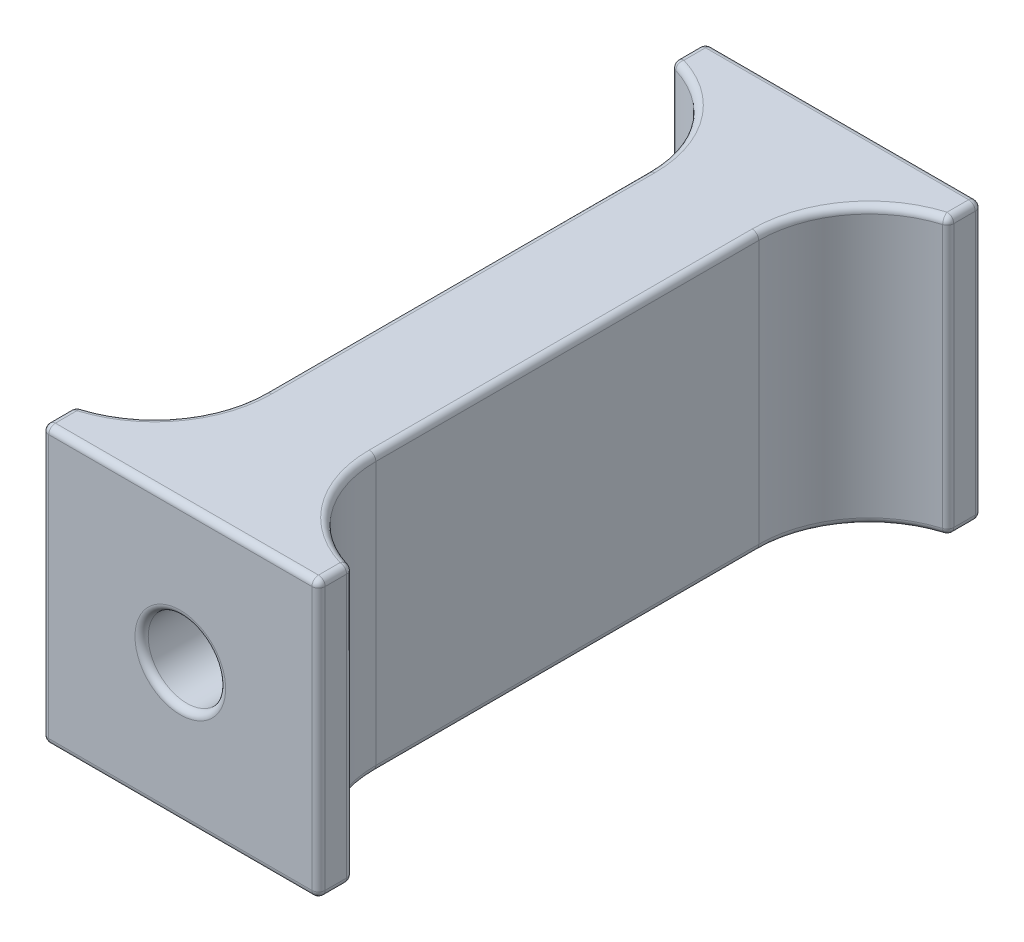
SolidWorks part; units mm, degrees
ref_plane "Alzado" through (0, 0, 0) normal (0, 0, 1) x (1, 0, 0)
ref_plane "Planta" through (0, 0, 0) normal (0, 1, 0) x (1, 0, 0)
ref_plane "Vista lateral" through (0, 0, 0) normal (1, 0, 0) x (0, 0, -1)
sketch "Croquis1" plane through (0, 0, 0) normal (0, 1, 0) x (1, 0, 0)
  line L0 (0, 0) -> (12.5, 0)
  line L1 (12.5, 0) -> (12.5, 3)
  line L2 (12.5, 3) -> (5, 3)
  line L3 (5, 3) -> (5, 30)
  line L4 (5, 30) -> (0, 30)
  line L5 (0, 30) -> (0, 0)
  dimension "D1" = 30
  dimension "D2" = 12.5
  dimension "D3" = 5
  dimension "D4" = 3
extrude "Saliente-Extruir1" add sketch "Croquis1" along normal blind 25
mirror "Simetría1" about plane through (0, 25, -30) normal (1, 0, 0) of "Saliente-Extruir1"
mirror "Simetría8" about plane through (5, 25, -30) normal (0, 0, 1) of bodies 102
ref_plane "Plano1" through (0, 0, -60) normal (0, 0, -1) x (-1, 0, 0)
sketch "Croquis2" plane through (0, 0, -60) normal (0, 0, -1) x (-1, 0, 0)
  line L0 (-12.5, 12.5) -> (12.5, 12.5) construction
  line L1 (-12.5, 25) -> (-12.5, 0) construction
  line L2 (12.5, 25) -> (12.5, 0) construction
  circle A0 centre (0, 12.5) radius 3.5
  dimension "D1" = 7
extrude "Cortar-Extruir1" cut sketch "Croquis2" against normal through all
fillet "Redondeo1" radius 10 4 edges at (5, 12.5, -57) (-5, 12.5, -57) (-5, 12.5, -3) (5, 12.5, -3)
fillet "Redondeo2" radius 0.6 34 edges at (-7.0943, 25, -53.4413) (7.0943, 25, -53.4413) (0, 25, 0) (-3.5, 12.5, 0) (-5, 25, -30) (5, 25, -30) (12.5, 12.5, -57) (12.5, 25, -58.5) (-12.5, 25, -58.5) (-12.5, 12.5, -57) (-12.5, 25, -1.5) (-12.5, 12.5, 0) (12.5, 12.5, 0) (12.5, 25, -1.5) (12.5, 0, -1.5) (5, 0, -30) (7.0943, 0, -53.4413) (12.5, 0, -58.5) (-12.5, 0, -58.5) (-7.0943, 0, -53.4413) (-5, 0, -30) (-12.5, 0, -1.5) (0, 0, 0) (12.5, 12.5, -60) (0, 25, -60) (-12.5, 12.5, -60) (0, 0, -60) (-3.5, 12.5, -60) (-7.0943, 25, -6.5587) (7.0943, 25, -6.5587) (-12.5, 12.5, -3) (12.5, 12.5, -3) (7.0943, 0, -6.5587) (-7.0943, 0, -6.5587)
